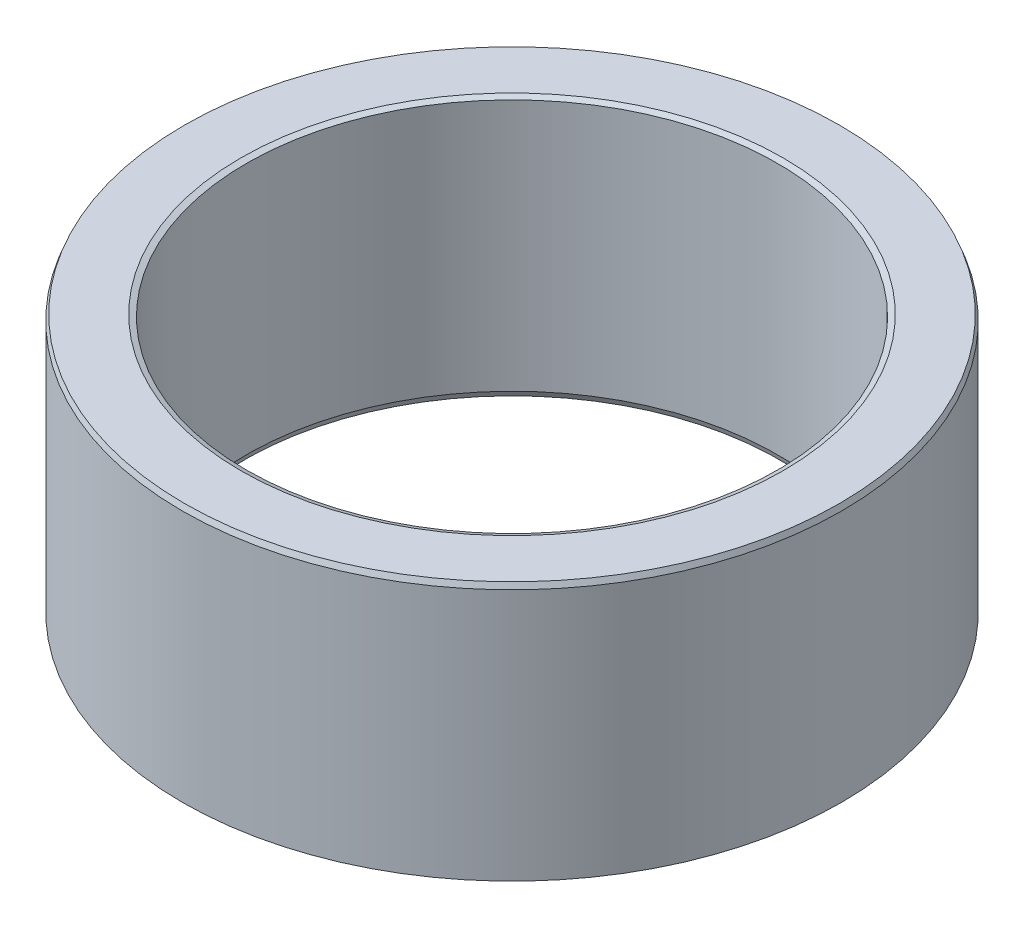
SolidWorks part; units mm, degrees
ref_plane "Front Plane" through (0, 0, 0) normal (0, 0, 1) x (1, 0, 0)
ref_plane "Top Plane" through (0, 0, 0) normal (0, 1, 0) x (1, 0, 0)
ref_plane "Right Plane" through (0, 0, 0) normal (1, 0, 0) x (0, 0, -1)
sketch "Sketch1" plane through (0, 0, 0) normal (0, 1, 0) x (1, 0, 0)
  circle A0 centre (0, 0) radius 57.5
  dimension "SLEEVE_OD" = 115
extrude "Boss-Extrude1" add sketch "Sketch1" along normal blind 45.3269
sketch "Sketch2" plane through (0, 0, 0) normal (0, 1, 0) x (1, 0, 0)
  circle A0 centre (0, 0) radius 46.318
  dimension "BORE_D" = 92.6359
extrude "Cut-Extrude1" cut sketch "Sketch2" along normal through all
chamfer "Chamfer1" distance 0.9545 angle 20.845 4 edges at (0, 45.3269, 46.318) (0, 0, 46.318) (0, 0, 57.5) (0, 45.3269, 57.5) first distance on face at (0, 45.3269, 46.318) first distance on face at (0, 0, 46.318) first distance on face at (0, 45.3269, 57.5)
